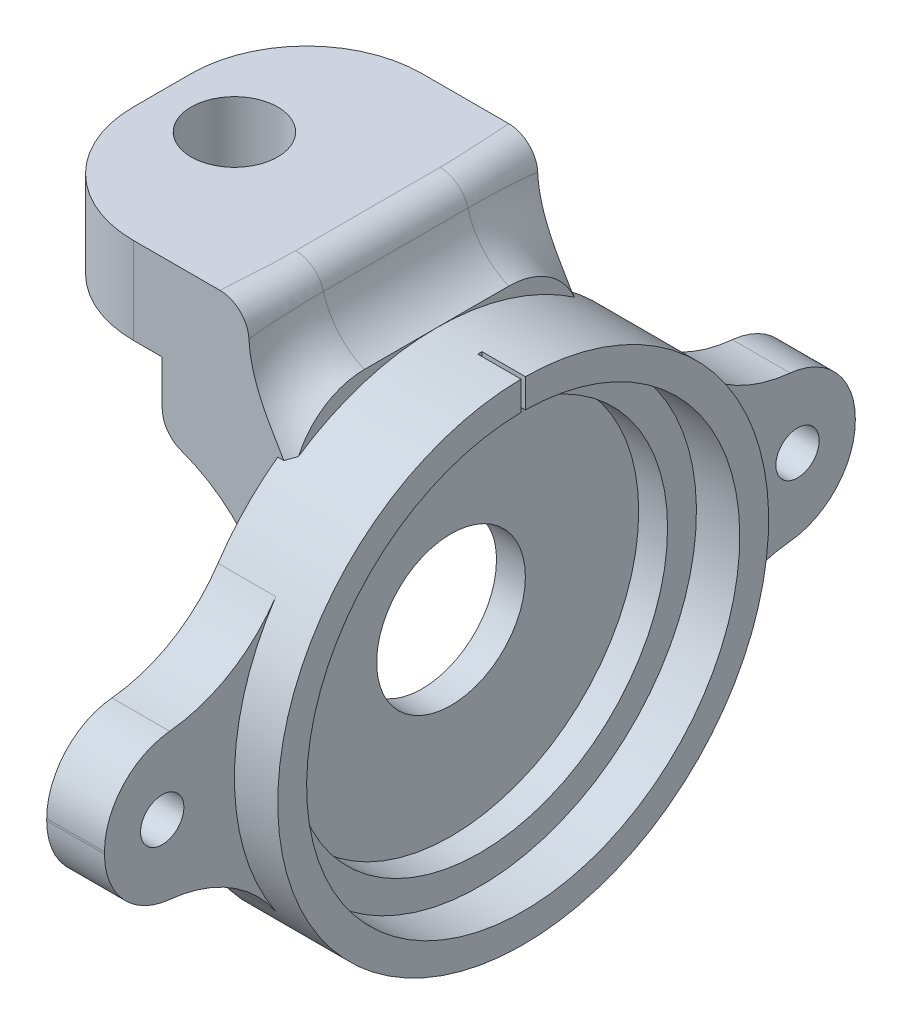
SolidWorks part; units mm, degrees
other "标注1"
sketch "草图7" plane through (10, -17, -25) normal (0.9745, -0.0318, -0.2219) x (0.2204, -0.0449, 0.9744)
ref_plane "前视基准面" through (0, 0, 0) normal (0, 0, 1) x (1, 0, 0)
ref_plane "上视基准面" through (0, 0, 0) normal (0, 1, 0) x (1, 0, 0)
ref_plane "右视基准面" through (0, 0, 0) normal (1, 0, 0) x (0, 0, -1)
other "Configuration Table"
sketch "草图1" plane through (0, 0, 0) normal (1, 0, 0) x (0, 0, -1)
  circle A0 centre (0, 0) radius 17
  dimension "D1" = 34
extrude "凸台-拉伸1" add sketch "草图1" along normal blind 7
sketch "草图5" plane through (0, 0, 0) normal (-1, 0, 0) x (0, 0, 1)
  line L0 (0, 0) -> (0, 10.6758) construction
  line L1 (0, 0) -> (14.1218, 0) construction
  line L2 (0, 5.0001) -> (26, 5.0001)
  line L3 (-26, 5.0001) -> (0, 5.0001)
  line L4 (-26, 5.0001) -> (-26, -4.9999)
  line L5 (-26, -4.9999) -> (11, -4.9999)
  line L7 (26, 5.0001) -> (26, -4.9999)
  line L8 (26, -4.9999) -> (11, -4.9999)
  point P10 (0, 0)
  point P12 (-5.9257, 3.063)
  dimension "D1" = 26
  dimension "D2" = 10
  dimension "D3" = 5.0001
  dimension "D4" = 26
extrude "凸台-拉伸2" add sketch "草图5" against normal blind 4
sketch "草图2" plane through (7, 0, 0) normal (1, 0, 0) x (0, 0, -1)
  circle A0 centre (0, 0) radius 15
  dimension "D1" = 30
extrude "切除-拉伸1" cut sketch "草图2" against normal blind 3
sketch "草图3" plane through (4, 0, 0) normal (1, 0, 0) x (0, 0, -1)
  circle A0 centre (0, 0) radius 5.15
  dimension "D1" = 10.3
extrude "切除-拉伸2" cut sketch "草图3" against normal up to next
sketch "草图4" plane through (4, 0, 0) normal (1, 0, 0) x (0, 0, -1)
  circle A0 centre (0, 0) radius 13
  dimension "D1" = 26
extrude "切除-拉伸3" cut sketch "草图4" against normal blind 2
sketch "草图6" plane through (4, 0, 0) normal (1, 0, 0) x (0, 0, -1)
  line L0 (-26, 0.0001) -> (26, 0.0001) construction
  line L1 (-26, -4.9999) -> (-26, 5.0001) construction
  line L2 (26, 5.0001) -> (26, -4.9999) construction
  circle A0 centre (-22, 0.0001) radius 1.5
  circle A1 centre (22, 0.0001) radius 1.5
  dimension "D1" = 3
  dimension "D2" = 3
  dimension "D3" = 4
  dimension "D4" = 4
extrude "切除-拉伸4" cut sketch "草图6" against normal up to next
fillet "圆角1" radius 10 4 edges at (2, 5.0001, -16.2481) (2, 5.0001, 16.2481) (2, -4.9999, 16.2481) (2, -4.9999, -16.2481)
fillet "圆角2" radius 5 4 edges at (2, 5.0001, 26) (2, -4.9999, 26) (2, -4.9999, -26) (2, 5.0001, -26)
sketch "草图8" plane through (7, 0, 0) normal (1, 0, 0) x (0, 0, -1)
  line L0 (0, 17) -> (0, 0) construction
  line L2 (-0.15, 17.2286) -> (0.15, 17.2286)
  line L3 (-0.15, 17.2286) -> (-0.15, 14.9992)
  line L4 (-0.15, 14.9992) -> (0.15, 14.9992)
  line L5 (0.15, 17.2286) -> (0.15, 14.9992)
  circle A1 centre (0, 0) radius 15 construction
  dimension "D1" = 0.3
  dimension "D2" = 0.15
extrude "切除-拉伸5" cut sketch "草图8" against normal up to surface (3 mm away) up to face at (4, 0, -13)
sketch "草图9" plane through (0, 0, 0) normal (-1, 0, 0) x (0, 0, 1)
  line L0 (-0.15, 16.9993) -> (0, 0) construction
  line L2 (-10, 13.7477) -> (10, 13.7477)
  line L3 (-10, 13.7477) -> (-10, 11.1529)
  line L4 (-10, 11.1529) -> (10, 11.1529)
  line L5 (10, 13.7477) -> (10, 11.1529)
  arc A0 (14.1351, 9.4445) -> (-14.1351, 9.4445) centre (0, 0) ccw construction
  dimension "D1" = 20
extrude "凸台-拉伸3" add sketch "草图9" along normal blind 8
sketch "草图10" plane through (0, 13.7477, 0) normal (0, 1, 0) x (1, 0, 0)
  line L0 (-8, -10) -> (0, -10) construction
  line L1 (-8, 10) -> (-2.004, 10)
  line L2 (-8, 10) -> (-8, -10)
  line L3 (-8, -10) -> (-2.004, -10)
  line L4 (-2.004, 10) -> (-2.004, -10)
  dimension "D1" = 5.996
extrude "凸台-拉伸4" add sketch "草图10" along normal blind 8
sketch "草图11" plane through (-8, 0, 0) normal (-1, 0, 0) x (0, 0, 1)
  line L0 (10, 11.1529) -> (10, 21.7477) construction
  line L1 (-10, 21.7477) -> (10, 21.7477)
  line L2 (-10, 21.7477) -> (-10, 15.7477)
  line L3 (-10, 15.7477) -> (10, 15.7477)
  line L4 (10, 21.7477) -> (10, 15.7477)
  dimension "D1" = 6
extrude "凸台-拉伸5" add sketch "草图11" along normal blind 10
sketch "草图12" plane through (0, 21.7477, 0) normal (0, 1, 0) x (1, 0, 0)
  line L0 (-18, 0) -> (-2.004, 0) construction
  line L1 (-18, -10) -> (-18, 10) construction
  line L2 (-2.004, -10) -> (-2.004, 10) construction
  circle A0 centre (-13, 0) radius 3
  dimension "D1" = 6
  dimension "D2" = 5
extrude "切除-拉伸6" cut sketch "草图12" against normal blind 10
fillet "圆角3" radius 10 1 edges at (0, 11.1529, 0)
sketch "草图13" plane through (-2.004, 0, 0) normal (1, 0, 0) x (0, 0, -1)
  line L0 (0, 21.7477) -> (0, 13) construction
  line L1 (-10, 21.7477) -> (10, 21.7477) construction
  line L2 (0, 17) -> (10, 17)
  line L3 (10, 21.7477) -> (10, 13.7477) construction
  line L4 (0, 17) -> (-10, 17)
  line L5 (-10, 21.7477) -> (-10, 13.7477) construction
  line L6 (-10, 17) -> (-10, 13.7477)
  line L7 (-10, 13.7477) -> (10, 13.7477)
  line L8 (10, 13.7477) -> (10, 17)
  circle A0 centre (0, 0) radius 13 construction
  arc A1 (0.15, 16.9993) -> (-0.15, 16.9993) centre (0, 0) ccw construction
extrude "凸台-拉伸6" add sketch "草图13" along normal blind 3
fillet "圆角5" radius 5 2 edges at (-0.504, 17, -10) (-0.504, 17, 10)
fillet "圆角6" radius 5 3 edges at (-2.004, 15.5355, -8.5355) (-2.004, 15.5355, 8.5355) (-2.004, 17, 0)
fillet "圆角7" radius 8 2 edges at (-18, 18.7477, -10) (-18, 18.7477, 10)
fillet "圆角9" radius 2 2 edges at (-2.004, 21.7477, 0) (-8, 11.1529, 0)
